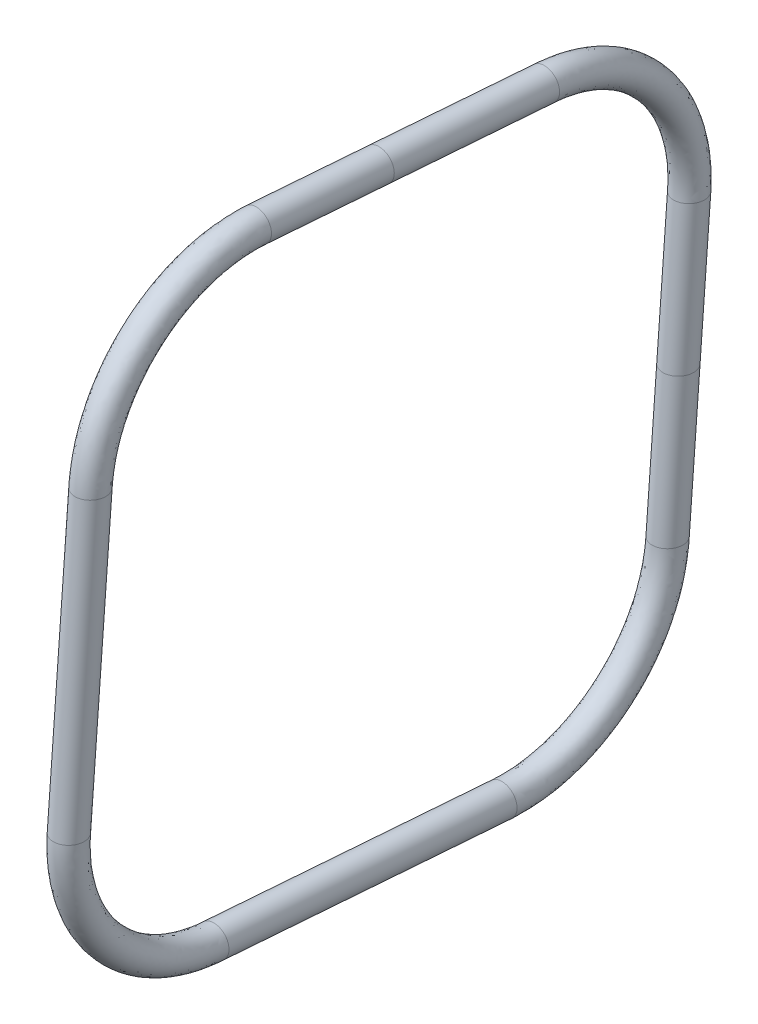
SolidWorks part; units mm, degrees
material "Rubber"
ref_plane "Front Plane" through (0, 0, 0) normal (0, 0, 1) x (1, 0, 0)
ref_plane "Top Plane" through (0, 0, 0) normal (0, 1, 0) x (1, 0, 0)
ref_plane "Right Plane" through (0, 0, 0) normal (1, 0, 0) x (0, 0, -1)
sketch "Sketch4" plane through (0, 0, 0) normal (1, 0, 0) x (0, 0, -1)
  line L0 (-33.6475, -14.0193) -> (-31.1849, 18.8731) construction
  line L1 (14.0193, -33.6475) -> (-18.8731, -31.1849) construction
  line L2 (-31.1849, 18.8731) -> (-31.0583, 18.8636)
  line L3 (-14.0288, 33.5208) -> (-14.0193, 33.6475)
  line L6 (32.4162, -2.4269) -> (31.1849, -18.8731) construction
  line L7 (33.6475, 14.0193) -> (32.4162, -2.4269) construction
  line L8 (-14.0193, 33.6475) -> (18.8731, 31.1849) construction
  line L9 (-33.6475, -14.0193) -> (-31.1849, 18.8731)
  line L10 (14.0193, -33.6475) -> (-18.8731, -31.1849)
  line L11 (32.4162, -2.4269) -> (31.1849, -18.8731)
  line L12 (33.6475, 14.0193) -> (32.4162, -2.4269)
  line L13 (-14.0193, 33.6475) -> (18.8731, 31.1849)
  arc A0 (-33.6475, -14.0193) -> (-18.8731, -31.1849) centre (-17.6775, -15.2149) ccw construction
  arc A1 (14.0193, -33.6475) -> (31.1849, -18.8731) centre (15.2149, -17.6775) ccw construction
  arc A2 (-14.0193, 33.6475) -> (-31.1849, 18.8731) centre (-15.2149, 17.6775) ccw
  arc A3 (-14.0288, 33.5208) -> (-31.0583, 18.8636) centre (-15.2149, 17.6775) ccw
  arc A4 (-14.0193, 33.6475) -> (-31.1849, 18.8731) centre (-15.2149, 17.6775) ccw
  arc A6 (33.6475, 14.0193) -> (18.8731, 31.1849) centre (17.6775, 15.2149) ccw construction
  arc A7 (-33.6475, -14.0193) -> (-18.8731, -31.1849) centre (-17.6775, -15.2149) ccw
  arc A8 (14.0193, -33.6475) -> (31.1849, -18.8731) centre (15.2149, -17.6775) ccw
  arc A9 (33.6475, 14.0193) -> (18.8731, 31.1849) centre (17.6775, 15.2149) ccw
  dimension "D1" = 0
sketch "Sketch3" plane through (0, 0, 0) normal (0, 0, 1) x (1, 0, 0)
  line L0 (0, 0) -> (-7.1671, 0) construction
  line L3 (-1.7399, 34.1034) -> (-1.7399, 31.6409) construction
  line L4 (-1.7399, 37.2442) -> (-1.7399, 34.7817) construction
  line L5 (-1.7399, 34.1034) -> (-1.7399, 31.6409)
  line L6 (0, 34.3632) -> (0, 0)
  line L7 (-1.7399, 37.2442) -> (-1.7399, 34.7817)
  line L8 (-1.7399, 34.1034) -> (-1.7399, 34.7817)
  ellipse E0 centre (0, 34.3632) end of major axis (0, 32.5979) minor radius 1.7399
  dimension "D1" = 3.5306
  dimension "D2" = 3.4798
ref_axis "Axis1" through (0, 0, 0) along (-1, 0, 0)
sweep "Sweep3" add profiles "Sketch3" path "Sketch4"
